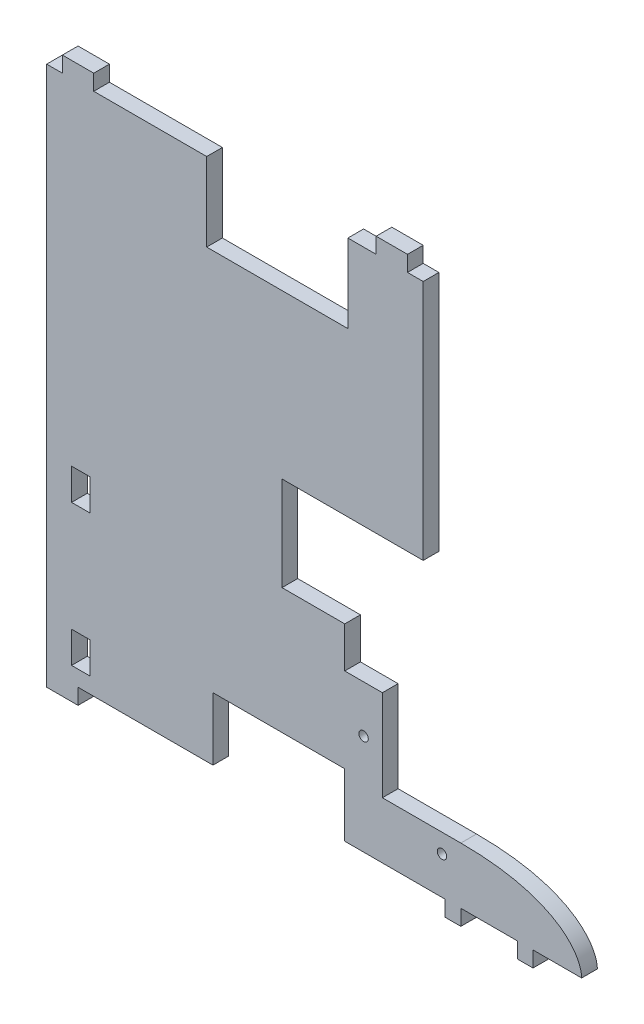
SolidWorks part; units mm, degrees
ref_plane "Plan de face" through (0, 0, 0) normal (0, 0, 1) x (1, 0, 0)
ref_plane "Plan de dessus" through (0, 0, 0) normal (0, 1, 0) x (1, 0, 0)
ref_plane "Plan de droite" through (0, 0, 0) normal (1, 0, 0) x (0, 0, -1)
sketch "Esquisse1" plane through (0, 0, 0) normal (0, 0, 1) x (1, 0, 0)
  line L1 (0, 0) -> (32, 0)
  line L2 (0, 0) -> (0, 47)
  line L3 (0, 47) -> (12, 47)
  line L4 (37, 0) -> (37, 18)
  line L6 (12, 47) -> (12, 18)
  line L7 (12, 18) -> (37, 18)
  line L8 (37, 0) -> (37, -5)
  line L9 (37, -5) -> (32, -5)
  line L10 (32, 0) -> (32, -5)
  circle A0 centre (6, 32) radius 1.5
  circle A1 centre (31, 12) radius 1.5
  dimension "D3" = 20
  dimension "D4" = 3
  dimension "D1" = 6
  dimension "D2" = 12
  dimension "D5" = 15
  dimension "D6" = 6
  dimension "D7" = 25
  dimension "D8" = 6
  dimension "D9" = 6
  dimension "D10" = 5
  dimension "D11" = 5
extrude "Boss.-Extru.1" add sketch "Esquisse1" along normal blind 5
sketch "Esquisse2" plane through (0, 0, 0) normal (0, 0, -1) x (-1, 0, 0)
  line L0 (-37, 18) -> (-12, 18) construction
  line L1 (-37, 0) -> (-55, 0)
  line L2 (-37, 0) -> (-37, 18)
  line L3 (-60, 0) -> (-75.5, 0)
  line L4 (42, 0) -> (85, 0)
  line L5 (0, 20) -> (0, 60)
  line L6 (0, 60) -> (20, 60)
  line L7 (-10, 167) -> (-1, 167)
  line L8 (0, 0) -> (-32, 0) construction
  line L9 (20, 60) -> (20, 90)
  line L10 (44, 167) -> (80, 167)
  line L11 (95, -5) -> (95, 167)
  line L12 (95, -5) -> (85, -5)
  line L13 (85, 0) -> (85, -5)
  line L14 (90, 167) -> (95, 167)
  line L15 (-60, 0) -> (-60, -5)
  line L16 (-60, -5) -> (-55, -5)
  line L17 (-55, 0) -> (-55, -5)
  line L18 (0, 20) -> (42, 20)
  line L19 (90, 167) -> (90, 172)
  line L20 (90, 172) -> (80, 172)
  line L21 (80, 167) -> (80, 172)
  line L22 (0, 47) -> (0, 0) construction
  line L23 (-20, 167) -> (-20, 172)
  line L24 (-20, 172) -> (-10, 172)
  line L25 (-10, 167) -> (-10, 172)
  line L26 (0, 0) -> (-32, 0) construction
  line L27 (42, 20) -> (42, 0)
  line L29 (-37, -5) -> (-37, 18) construction
  line L30 (-1, 167) -> (-1, 142)
  line L31 (20, 90) -> (-25, 90)
  line L32 (-1, 142) -> (44, 142)
  line L33 (-20, 167) -> (-25, 167)
  line L34 (-25, 90) -> (-25, 167)
  line L35 (44, 167) -> (44, 142)
  line L36 (81.157, 60) -> (87.0635, 60)
  line L37 (81.157, 60) -> (81.157, 50)
  line L38 (81.157, 50) -> (87.0635, 50)
  line L39 (87.0635, 60) -> (87.0635, 50)
  line L47 (87.0635, 15) -> (81.157, 15)
  line L48 (87.0635, 15) -> (87.0635, 5)
  line L49 (87.0635, 5) -> (81.157, 5)
  line L50 (81.157, 15) -> (81.157, 5)
  spline S0 degree 3 poles (-75.5, 0) (-75.5, 5.9822) (-67.6854, 18) (-37, 18) knots 0 0 0 0 1 1 1 1
  dimension "D1" = 38.5
  dimension "D2" = 20
  dimension "D3" = 167
  dimension "D4" = 95
  dimension "D5" = 5
  dimension "D6" = 30
  dimension "D7" = 5
  dimension "D8" = 10
  dimension "D9" = 10
  dimension "D10" = 10
  dimension "D11" = 140
  dimension "D12" = 5
  dimension "D13" = 42
  dimension "D14" = 20
  dimension "D15" = 40
  dimension "D16" = 45
  dimension "D17" = 5
  dimension "D18" = 5
  dimension "D19" = 25
  dimension "D20" = 45
  dimension "D21" = 24
  dimension "D22" = 10
extrude "Boss.-Extru.2" add sketch "Esquisse2" against normal blind 5
